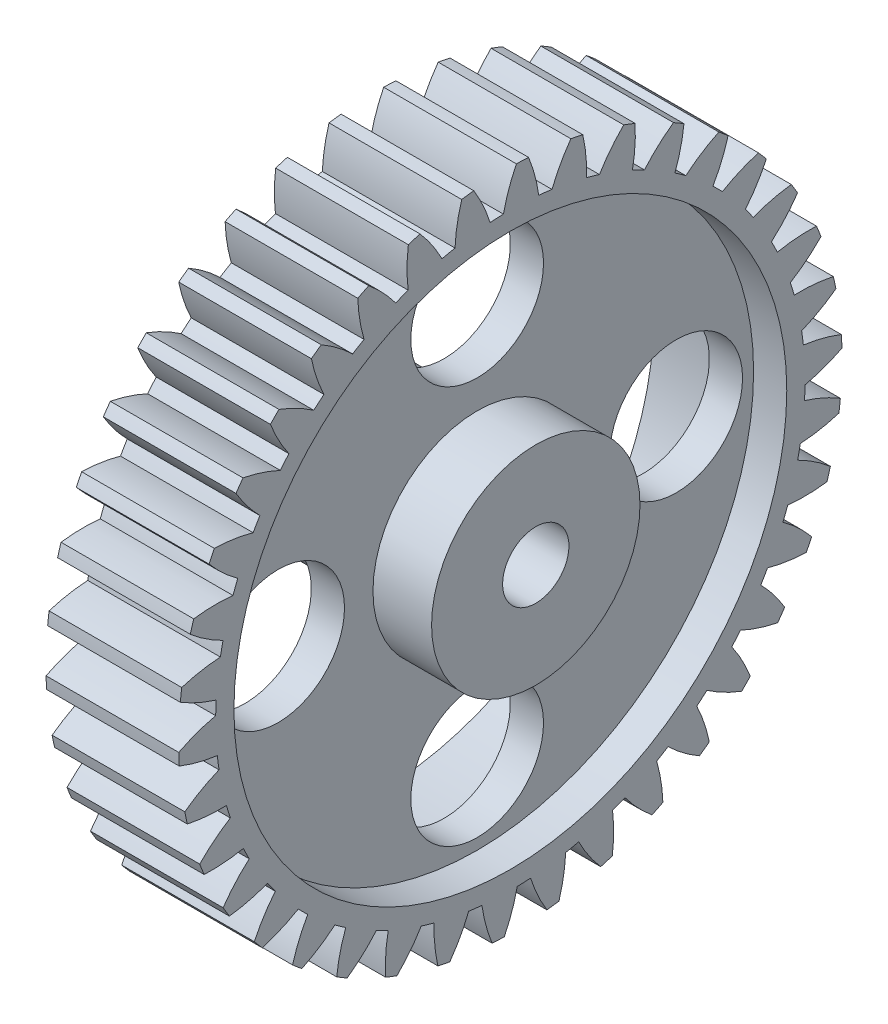
SolidWorks part; units mm, degrees
ref_plane "Front Plane" through (0, 0, 0) normal (0, 0, 1) x (1, 0, 0)
ref_plane "Top Plane" through (0, 0, 0) normal (0, 1, 0) x (1, 0, 0)
ref_plane "Right Plane" through (0, 0, 0) normal (1, 0, 0) x (0, 0, -1)
sketch "Sketch1" plane through (0, 0, 0) normal (1, 0, 0) x (0, 0, -1)
  line L0 (0, 0) -> (0.1096, 2.998) construction
  line L1 (0.9733, 26.6322) -> (1.0957, 29.98) construction
  circle A0 centre (0, 0) radius 30 construction
  circle A1 centre (0, 0) radius 28.75 construction
  circle A2 centre (0, 0) radius 26.65 construction
  circle A3 centre (0, 0) radius 3
  arc A4 (0, 28.75) -> (2.0986, 28.6733) centre (0, 0) cw
  arc A5 (-0.6274, 26.6426) -> (2.5705, 26.5257) centre (0, 0) cw
  arc A6 (0.5458, 29.995) -> (1.6451, 29.9549) centre (0, 0) cw
  arc A7 (1.6451, 29.9549) -> (2.5705, 26.5257) centre (-11.6684, 24.5227) cw
  arc A8 (0.5458, 29.995) -> (-0.6274, 26.6426) centre (13.4273, 23.6055) ccw
  arc A9 (5.4754, 29.4961) -> (3.7664, 26.3825) centre (17.1295, 21.0735) ccw
  arc A10 (3.7664, 26.3825) -> (6.9014, 25.7409) centre (0, 0) cw
  arc A11 (6.5531, 29.2755) -> (6.9014, 25.7409) centre (-7.4729, 26.1088) cw
  arc A12 (5.4754, 29.4961) -> (6.5531, 29.2755) centre (0, 0) cw
  arc A13 (10.2556, 28.1926) -> (8.0575, 25.4028) centre (20.3644, 17.9667) ccw
  arc A14 (8.0575, 25.4028) -> (11.0441, 24.2539) centre (0, 0) cw
  arc A15 (11.2823, 27.7977) -> (11.0441, 24.2539) centre (-3.0736, 26.9827) cw
  arc A16 (10.2556, 28.1926) -> (11.2823, 27.7977) centre (0, 0) cw
  arc A17 (14.7561, 26.1201) -> (12.1287, 23.7301) centre (23.0439, 14.3698) ccw
  arc A18 (12.1287, 23.7301) -> (14.8855, 22.1053) centre (0, 0) cw
  arc A19 (15.7038, 25.5615) -> (14.8855, 22.1053) centre (1.4095, 27.1206) cw
  arc A20 (14.7561, 26.1201) -> (15.7038, 25.5615) centre (0, 0) cw
  arc A21 (18.8541, 23.335) -> (15.8691, 21.4101) centre (25.0948, 10.3809) ccw
  arc A22 (15.8691, 21.4101) -> (18.3209, 19.3537) centre (0, 0) cw
  arc A23 (19.6969, 22.6282) -> (18.3209, 19.3537) centre (5.8542, 26.5187) cw
  arc A24 (18.8541, 23.335) -> (19.6969, 22.6282) centre (0, 0) cw
  arc A25 (22.4377, 19.9135) -> (19.1767, 18.5061) centre (26.4612, 6.1088) ccw
  arc A26 (19.1767, 18.5061) -> (21.2566, 16.0742) centre (0, 0) cw
  arc A27 (23.1527, 19.0775) -> (21.2566, 16.0742) centre (10.1392, 25.1934) cw
  arc A28 (22.4377, 19.9135) -> (23.1527, 19.0775) centre (0, 0) cw
  arc A29 (25.4094, 15.9488) -> (21.9612, 15.0974) centre (27.1058, 1.6702) ccw
  arc A30 (21.9612, 15.0974) -> (23.6124, 12.3563) centre (0, 0) cw
  arc A31 (25.977, 15.0065) -> (23.6124, 12.3563) centre (14.1476, 23.181) cw
  arc A32 (25.4094, 15.9488) -> (25.977, 15.0065) centre (0, 0) cw
  arc A33 (27.6879, 11.549) -> (24.1466, 11.2768) centre (27.011, -2.8141) ccw
  arc A34 (24.1466, 11.2768) -> (25.3241, 8.3013) centre (0, 0) cw
  arc A35 (28.0927, 10.5262) -> (25.3241, 8.3013) centre (17.7701, 20.5362) cw
  arc A36 (27.6879, 11.549) -> (28.0927, 10.5262) centre (0, 0) cw
  arc A37 (29.2112, 6.8342) -> (25.6733, 7.1486) centre (26.1794, -7.2216) ccw
  arc A38 (25.6733, 7.1486) -> (26.3451, 4.0199) centre (0, 0) cw
  arc A39 (29.4421, 5.7587) -> (26.3451, 4.0199) centre (20.9079, 17.3313) cw
  arc A40 (29.2112, 6.8342) -> (29.4421, 5.7587) centre (0, 0) cw
  arc A41 (29.9377, 1.933) -> (26.4998, 2.8254) centre (24.6337, -11.4321) ccw
  arc A42 (26.4998, 2.8254) -> (26.6474, -0.3712) centre (0, 0) cw
  arc A43 (29.9884, 0.8342) -> (26.6474, -0.3712) centre (23.4754, 13.6536) cw
  arc A44 (29.9377, 1.933) -> (29.9884, 0.8342) centre (0, 0) cw
  arc A45 (29.8475, -3.0209) -> (26.6034, -1.5749) centre (22.4161, -15.3307) ccw
  arc A46 (26.6034, -1.5749) -> (26.2229, -4.7522) centre (0, 0) cw
  arc A47 (29.7167, -4.1131) -> (26.2229, -4.7522) centre (25.4025, 9.6034) cw
  arc A48 (29.8475, -3.0209) -> (29.7167, -4.1131) centre (0, 0) cw
  arc A49 (28.9432, -7.8925) -> (25.9814, -5.9322) centre (19.587, -18.8112) ccw
  arc A50 (25.9814, -5.9322) -> (25.083, -9.0035) centre (0, 0) cw
  arc A51 (28.6344, -8.9482) -> (25.083, -9.0035) centre (26.6367, 5.2913) cw
  arc A52 (28.9432, -7.8925) -> (28.6344, -8.9482) centre (0, 0) cw
  arc A53 (27.2494, -12.5487) -> (24.6506, -10.1277) centre (16.2236, -21.7786) ccw
  arc A54 (24.6506, -10.1277) -> (23.259, -13.0092) centre (0, 0) cw
  arc A55 (26.771, -13.5393) -> (23.259, -13.0092) centre (27.1443, 0.8349) cw
  arc A56 (27.2494, -12.5487) -> (26.771, -13.5393) centre (0, 0) cw
  arc A57 (24.8123, -16.8627) -> (22.6474, -14.0469) centre (12.4177, -24.1518) ccw
  arc A58 (22.6474, -14.0469) -> (20.8005, -16.6601) centre (0, 0) cw
  arc A59 (24.1774, -17.761) -> (20.8005, -16.6601) centre (26.9115, -3.6443) cw
  arc A60 (24.8123, -16.8627) -> (24.1774, -17.761) centre (0, 0) cw
  arc A61 (21.6984, -20.7167) -> (20.0265, -17.583) centre (8.2731, -25.8663) ccw
  arc A62 (20.0265, -17.583) -> (17.7747, -19.8566) centre (0, 0) cw
  arc A63 (20.9243, -21.4982) -> (17.7747, -19.8566) centre (25.9447, -8.0241) cw
  arc A64 (21.6984, -20.7167) -> (20.9243, -21.4982) centre (0, 0) cw
  arc A65 (17.9926, -24.0056) -> (16.8593, -20.6394) centre (3.9028, -26.8753) ccw
  arc A66 (16.8593, -20.6394) -> (14.264, -22.5114) centre (0, 0) cw
  arc A67 (17.1004, -24.649) -> (14.264, -22.5114) centre (24.2701, -12.185) cw
  arc A68 (17.9926, -24.0056) -> (17.1004, -24.649) centre (0, 0) cw
  arc A69 (13.796, -26.6396) -> (13.2323, -23.1329) centre (-0.5739, -27.1511) ccw
  arc A70 (13.2323, -23.1329) -> (10.3642, -24.5521) centre (0, 0) cw
  arc A71 (12.8101, -27.1275) -> (10.3642, -24.5521) centre (21.9335, -16.0135) cw
  arc A72 (13.796, -26.6396) -> (12.8101, -27.1275) centre (0, 0) cw
  arc A73 (9.2231, -28.5471) -> (9.2442, -24.9953) centre (-5.035, -26.6863) ccw
  arc A74 (9.2442, -24.9953) -> (6.1817, -25.9231) centre (0, 0) cw
  arc A75 (8.1704, -28.866) -> (6.1817, -25.9231) centre (18.9986, -19.4053) cw
  arc A76 (9.2231, -28.5471) -> (8.1704, -28.866) centre (0, 0) cw
  arc A77 (4.3986, -29.6758) -> (5.0041, -26.176) centre (-9.3588, -25.4936) ccw
  arc A78 (5.0041, -26.176) -> (1.8306, -26.5871) centre (0, 0) cw
  arc A79 (3.3077, -29.8171) -> (1.8306, -26.5871) centre (15.5455, -22.2677) cw
  arc A80 (4.3986, -29.6758) -> (3.3077, -29.8171) centre (0, 0) cw
  arc A81 (-0.5458, -29.995) -> (0.6274, -26.6426) centre (-13.4273, -23.6055) ccw
  arc A82 (0.6274, -26.6426) -> (-2.5705, -26.5257) centre (0, 0) cw
  arc A83 (-1.6451, -29.9549) -> (-2.5705, -26.5257) centre (11.6684, -24.5227) cw
  arc A84 (-0.5458, -29.995) -> (-1.6451, -29.9549) centre (0, 0) cw
  arc A85 (-5.4754, -29.4961) -> (-3.7664, -26.3825) centre (-17.1295, -21.0735) ccw
  arc A86 (-3.7664, -26.3825) -> (-6.9014, -25.7409) centre (0, 0) cw
  arc A87 (-6.5531, -29.2755) -> (-6.9014, -25.7409) centre (7.4729, -26.1088) cw
  arc A88 (-5.4754, -29.4961) -> (-6.5531, -29.2755) centre (0, 0) cw
  arc A89 (-10.2556, -28.1926) -> (-8.0575, -25.4028) centre (-20.3644, -17.9667) ccw
  arc A90 (-8.0575, -25.4028) -> (-11.0441, -24.2539) centre (0, 0) cw
  arc A91 (-11.2823, -27.7977) -> (-11.0441, -24.2539) centre (3.0736, -26.9827) cw
  arc A92 (-10.2556, -28.1926) -> (-11.2823, -27.7977) centre (0, 0) cw
  arc A93 (-14.7561, -26.1201) -> (-12.1287, -23.7301) centre (-23.0439, -14.3698) ccw
  arc A94 (-12.1287, -23.7301) -> (-14.8855, -22.1053) centre (0, 0) cw
  arc A95 (-15.7038, -25.5615) -> (-14.8855, -22.1053) centre (-1.4095, -27.1206) cw
  arc A96 (-14.7561, -26.1201) -> (-15.7038, -25.5615) centre (0, 0) cw
  arc A97 (-18.8541, -23.335) -> (-15.8691, -21.4101) centre (-25.0948, -10.3809) ccw
  arc A98 (-15.8691, -21.4101) -> (-18.3209, -19.3537) centre (0, 0) cw
  arc A99 (-19.6969, -22.6282) -> (-18.3209, -19.3537) centre (-5.8542, -26.5187) cw
  arc A100 (-18.8541, -23.335) -> (-19.6969, -22.6282) centre (0, 0) cw
  arc A101 (-22.4377, -19.9135) -> (-19.1767, -18.5061) centre (-26.4612, -6.1088) ccw
  arc A102 (-19.1767, -18.5061) -> (-21.2566, -16.0742) centre (0, 0) cw
  arc A103 (-23.1527, -19.0775) -> (-21.2566, -16.0742) centre (-10.1392, -25.1934) cw
  arc A104 (-22.4377, -19.9135) -> (-23.1527, -19.0775) centre (0, 0) cw
  arc A105 (-25.4094, -15.9488) -> (-21.9612, -15.0974) centre (-27.1058, -1.6702) ccw
  arc A106 (-21.9612, -15.0974) -> (-23.6124, -12.3563) centre (0, 0) cw
  arc A107 (-25.977, -15.0065) -> (-23.6124, -12.3563) centre (-14.1476, -23.181) cw
  arc A108 (-25.4094, -15.9488) -> (-25.977, -15.0065) centre (0, 0) cw
  arc A109 (-27.6879, -11.549) -> (-24.1466, -11.2768) centre (-27.011, 2.8141) ccw
  arc A110 (-24.1466, -11.2768) -> (-25.3241, -8.3013) centre (0, 0) cw
  arc A111 (-28.0927, -10.5262) -> (-25.3241, -8.3013) centre (-17.7701, -20.5362) cw
  arc A112 (-27.6879, -11.549) -> (-28.0927, -10.5262) centre (0, 0) cw
  arc A113 (-29.2112, -6.8342) -> (-25.6733, -7.1486) centre (-26.1794, 7.2216) ccw
  arc A114 (-25.6733, -7.1486) -> (-26.3451, -4.0199) centre (0, 0) cw
  arc A115 (-29.4421, -5.7587) -> (-26.3451, -4.0199) centre (-20.9079, -17.3313) cw
  arc A116 (-29.2112, -6.8342) -> (-29.4421, -5.7587) centre (0, 0) cw
  arc A117 (-29.9377, -1.933) -> (-26.4998, -2.8254) centre (-24.6337, 11.4321) ccw
  arc A118 (-26.4998, -2.8254) -> (-26.6474, 0.3712) centre (0, 0) cw
  arc A119 (-29.9884, -0.8342) -> (-26.6474, 0.3712) centre (-23.4754, -13.6536) cw
  arc A120 (-29.9377, -1.933) -> (-29.9884, -0.8342) centre (0, 0) cw
  arc A121 (-29.8475, 3.0209) -> (-26.6034, 1.5749) centre (-22.4161, 15.3307) ccw
  arc A122 (-26.6034, 1.5749) -> (-26.2229, 4.7522) centre (0, 0) cw
  arc A123 (-29.7167, 4.1131) -> (-26.2229, 4.7522) centre (-25.4025, -9.6034) cw
  arc A124 (-29.8475, 3.0209) -> (-29.7167, 4.1131) centre (0, 0) cw
  arc A125 (-28.9432, 7.8925) -> (-25.9814, 5.9322) centre (-19.587, 18.8112) ccw
  arc A126 (-25.9814, 5.9322) -> (-25.083, 9.0035) centre (0, 0) cw
  arc A127 (-28.6344, 8.9482) -> (-25.083, 9.0035) centre (-26.6367, -5.2913) cw
  arc A128 (-28.9432, 7.8925) -> (-28.6344, 8.9482) centre (0, 0) cw
  arc A129 (-27.2494, 12.5487) -> (-24.6506, 10.1277) centre (-16.2236, 21.7786) ccw
  arc A130 (-24.6506, 10.1277) -> (-23.259, 13.0092) centre (0, 0) cw
  arc A131 (-26.771, 13.5393) -> (-23.259, 13.0092) centre (-27.1443, -0.8349) cw
  arc A132 (-27.2494, 12.5487) -> (-26.771, 13.5393) centre (0, 0) cw
  arc A133 (-24.8123, 16.8627) -> (-22.6474, 14.0469) centre (-12.4177, 24.1518) ccw
  arc A134 (-22.6474, 14.0469) -> (-20.8005, 16.6601) centre (0, 0) cw
  arc A135 (-24.1774, 17.761) -> (-20.8005, 16.6601) centre (-26.9115, 3.6443) cw
  arc A136 (-24.8123, 16.8627) -> (-24.1774, 17.761) centre (0, 0) cw
  arc A137 (-21.6984, 20.7167) -> (-20.0265, 17.583) centre (-8.2731, 25.8663) ccw
  arc A138 (-20.0265, 17.583) -> (-17.7747, 19.8566) centre (0, 0) cw
  arc A139 (-20.9243, 21.4982) -> (-17.7747, 19.8566) centre (-25.9447, 8.0241) cw
  arc A140 (-21.6984, 20.7167) -> (-20.9243, 21.4982) centre (0, 0) cw
  arc A141 (-17.9926, 24.0056) -> (-16.8593, 20.6394) centre (-3.9028, 26.8753) ccw
  arc A142 (-16.8593, 20.6394) -> (-14.264, 22.5114) centre (0, 0) cw
  arc A143 (-17.1004, 24.649) -> (-14.264, 22.5114) centre (-24.2701, 12.185) cw
  arc A144 (-17.9926, 24.0056) -> (-17.1004, 24.649) centre (0, 0) cw
  arc A145 (-13.796, 26.6396) -> (-13.2323, 23.1329) centre (0.5739, 27.1511) ccw
  arc A146 (-13.2323, 23.1329) -> (-10.3642, 24.5521) centre (0, 0) cw
  arc A147 (-12.8101, 27.1275) -> (-10.3642, 24.5521) centre (-21.9335, 16.0135) cw
  arc A148 (-13.796, 26.6396) -> (-12.8101, 27.1275) centre (0, 0) cw
  arc A149 (-9.2231, 28.5471) -> (-9.2442, 24.9953) centre (5.035, 26.6863) ccw
  arc A150 (-9.2442, 24.9953) -> (-6.1817, 25.9231) centre (0, 0) cw
  arc A151 (-8.1704, 28.866) -> (-6.1817, 25.9231) centre (-18.9986, 19.4053) cw
  arc A152 (-9.2231, 28.5471) -> (-8.1704, 28.866) centre (0, 0) cw
  arc A153 (-4.3986, 29.6758) -> (-5.0041, 26.176) centre (9.3588, 25.4936) ccw
  arc A154 (-5.0041, 26.176) -> (-1.8306, 26.5871) centre (0, 0) cw
  arc A155 (-3.3077, 29.8171) -> (-1.8306, 26.5871) centre (-15.5455, 22.2677) cw
  arc A156 (-4.3986, 29.6758) -> (-3.3077, 29.8171) centre (0, 0) cw
  circle A229 centre (0, 0) radius 26.65
  circle A230 centre (0, 0) radius 18 construction
  circle A231 centre (0, 18) radius 6
  circle A232 centre (18, 0) radius 6
  circle A233 centre (0, -18) radius 6
  circle A234 centre (-18, 0) radius 6
  point P13 (0.9733, 26.6322)
  point P16 (1.0957, 29.98)
  point P254 (0, 0)
  point P351 (0, 0)
  dimension "D1" = 60
  dimension "D2" = 57.5
  dimension "D3" = 53.3
  dimension "D4" = 6
  dimension "D5" = 2.1
  dimension "D9" = 53.3
  dimension "D10" = 4
  dimension "D6" = 3.2
  dimension "D7" = 1.1
  dimension "D8" = 38
extrude "Boss-Extrude1" add sketch "Sketch1" along normal blind 12 contours A62 A229 A58 A54 A50 A46 A42 A38 A34 A30 A26 A22 A18 A14 A10 A5 | A144 A141 A142 A143 | A140 A137 A138 A139 | A136 A133 A134 A135 | A132 A129 A130 A131 | A128 A125 A126 A127 | A124 A121 A122 A123 | A120 A117 A118 A119 | A116 A113 A114 A115 | A112 A109 A110 A111 | A108 A105 A106 A107 | A104 A101 A102 A103 | A100 A97 A98 A99 | A96 A93 A94 A95 | A92 A89 A90 A91 | A88 A85 A86 A87 | A84 A81 A82 A83 | A148 A145 A146 A147 | A152 A149 A150 A151 | A156 A153 A154 A155 | A60 A57 A58 A59 | A64 A61 A62 A63 | A68 A65 A66 A67 | A72 A69 A70 A71 | A76 A73 A74 A75 | A80 A77 A78 A79 | A12 A9 A10 A11 | A16 A13 A14 A15 | A20 A17 A18 A19 | A56 A53 A54 A55 | A52 A49 A50 A51 | A48 A45 A46 A47 | A44 A41 A42 A43 | A40 A37 A38 A39 | A36 A33 A34 A35 | A32 A29 A30 A31 | A28 A25 A26 A27 | A24 A21 A22 A23 | A6 A8 A4 A7 | A4 A8 A5 A7 region at (0, 29.2871, -1.0703) region at (0, 27.5989, -1.0086) region at (0, 25.8789, -0.9458) region at (0, 27.8289, 3.6048) region at (0, 27.4915, -5.6265) region at (0, 26.856, 8.1361) region at (0, 26.1905, -10.0748) region at (0, 25.1506, 12.4455) region at (0, 24.175, -14.2482) region at (0, 22.7591, 16.4154) region at (0, 21.5001, -18.0329) region at (0, 19.7468, 19.9375) region at (0, 18.2388, -21.3258) region at (0, 16.1959, 22.9158) region at (0, 14.4799, -24.0369) region at (0, 12.2031, 25.269) region at (0, 10.3261, -26.0924) region at (0, 7.8776, 26.933) region at (0, 5.8906, -27.4362) region at (0, 3.3371, 27.8623) region at (0, 1.2944, -28.0315) region at (0, -1.2944, 28.0315) region at (0, -3.3371, -27.8623) region at (0, -5.8906, 27.4362) region at (0, -7.8776, -26.933) region at (0, -10.3261, 26.0924) region at (0, -12.2031, -25.269) region at (0, -14.4799, 24.0369) region at (0, -16.1959, -22.9158) region at (0, -18.2388, 21.3258) region at (0, -19.7468, -19.9375) region at (0, -21.5001, 18.0329) region at (0, -22.7591, -16.4154) region at (0, -24.175, 14.2482) region at (0, -25.1506, -12.4455) region at (0, -26.1905, 10.0748) region at (0, -26.856, -8.1361) region at (0, -27.4915, 5.6265) region at (0, -27.8289, -3.6048) region at (0, -28.0427, 1.0249)
sketch "Sketch2" plane through (12, 0, 0) normal (1, 0, 0) x (0, 0, -1)
  circle A0 centre (0, 0) radius 9.425
  circle A1 centre (0, 0) radius 3
  dimension "D1" = 6
  dimension "D2" = 18.85
extrude "Boss-Extrude2" add sketch "Sketch2" along normal blind 2.3 and the other way blind 3
sketch "Sketch3" plane through (0, 0, 0) normal (-1, 0, 0) x (0, 0, 1)
  circle A0 centre (0, 0) radius 7.325
  circle A1 centre (0, 0) radius 3
  dimension "D1" = 6
  dimension "D2" = 14.65
extrude "Boss-Extrude3" add sketch "Sketch3" along normal blind 8.3 and the other way blind 6
sketch "Sketch4" plane through (12, 0, 0) normal (1, 0, 0) x (0, 0, -1)
  circle A0 centre (0, 0) radius 25
  circle A1 centre (0, 0) radius 9.425
extrude "Cut-Extrude1" cut sketch "Sketch4" against normal blind 3
sketch "Sketch5" plane through (0, 0, 0) normal (-1, 0, 0) x (0, 0, 1)
  circle A0 centre (0, 0) radius 25
  circle A1 centre (0, 0) radius 7.325
extrude "Cut-Extrude2" cut sketch "Sketch5" against normal blind 6
